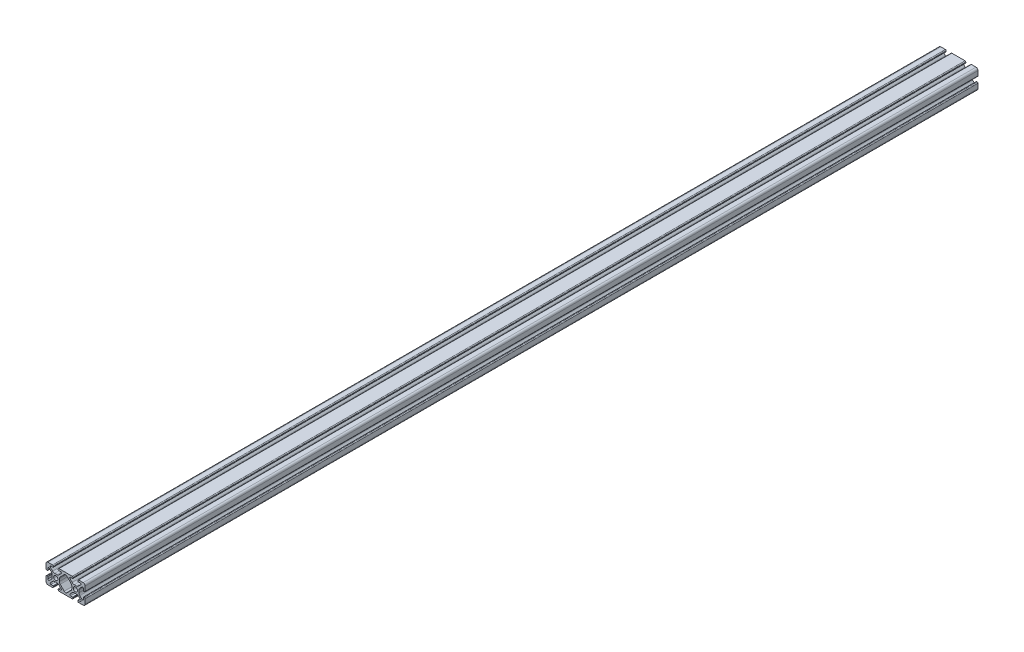
SolidWorks part; units mm, degrees
ref_plane "Plan de face" through (0, 0, 0) normal (0, 0, 1) x (1, 0, 0)
ref_plane "Plan de dessus" through (0, 0, 0) normal (0, 1, 0) x (1, 0, 0)
ref_plane "Plan de droite" through (0, 0, 0) normal (1, 0, 0) x (0, 0, -1)
ref_plane "Plan1" through (0, 0, 0) normal (0, 0, -1) x (-1, 0, 0)
sketch "Esquisse1" plane through (0, 0, 0) normal (0, 0, -1) x (-1, 0, 0)
  line L0 (-40, 6.7) -> (-40, 2)
  line L1 (-38, 0) -> (-33.3, 0)
  line L2 (-32.5, 0.8) -> (-32.5, 1.5)
  line L3 (-32.8, 1.8) -> (-34.9184, 1.8)
  line L4 (-35.5064, 3.2196) -> (-33.2547, 5.4713)
  line L5 (-31.1334, 6.35) -> (-28.8666, 6.35)
  line L6 (-26.7453, 5.4713) -> (-24.4936, 3.2196)
  line L7 (-25.0816, 1.8) -> (-27.2, 1.8)
  line L8 (-27.5, 1.5) -> (-27.5, 0.8)
  line L9 (-26.7, 0) -> (-13.3, 0)
  line L10 (-12.5, 0.8) -> (-12.5, 1.5)
  line L11 (-12.8, 1.8) -> (-14.9184, 1.8)
  line L12 (-15.5064, 3.2196) -> (-13.2547, 5.4713)
  line L13 (-11.1334, 6.35) -> (-8.8666, 6.35)
  line L14 (-6.7453, 5.4713) -> (-4.4936, 3.2196)
  line L15 (-5.0816, 1.8) -> (-7.2, 1.8)
  line L16 (-7.5, 1.5) -> (-7.5, 0.8)
  line L17 (-6.7, 0) -> (-2, 0)
  line L18 (0, 2) -> (0, 6.7)
  line L19 (-0.8, 7.5) -> (-1.5, 7.5)
  line L20 (-1.8, 7.2) -> (-1.8, 5.0816)
  line L21 (-3.2196, 4.4936) -> (-5.4713, 6.7453)
  line L22 (-6.35, 8.8666) -> (-6.35, 11.1334)
  line L23 (-5.4713, 13.2547) -> (-3.2196, 15.5064)
  line L24 (-1.8, 14.9184) -> (-1.8, 12.8)
  line L25 (-1.5, 12.5) -> (-0.8, 12.5)
  line L26 (0, 13.3) -> (0, 18)
  line L27 (-2, 20) -> (-6.7, 20)
  line L28 (-7.5, 19.2) -> (-7.5, 18.5)
  line L29 (-7.2, 18.2) -> (-5.0816, 18.2)
  line L30 (-4.4936, 16.7804) -> (-6.7453, 14.5287)
  line L31 (-8.8666, 13.65) -> (-11.1334, 13.65)
  line L32 (-13.2547, 14.5287) -> (-15.5064, 16.7804)
  line L33 (-14.9184, 18.2) -> (-12.8, 18.2)
  line L34 (-12.5, 18.5) -> (-12.5, 19.2)
  line L35 (-13.3, 20) -> (-26.7, 20)
  line L36 (-27.5, 19.2) -> (-27.5, 18.5)
  line L37 (-27.2, 18.2) -> (-25.0816, 18.2)
  line L38 (-24.4936, 16.7804) -> (-26.7453, 14.5287)
  line L39 (-28.8666, 13.65) -> (-31.1334, 13.65)
  line L40 (-33.2547, 14.5287) -> (-35.5064, 16.7804)
  line L41 (-34.9184, 18.2) -> (-32.8, 18.2)
  line L42 (-32.5, 18.5) -> (-32.5, 19.2)
  line L43 (-33.3, 20) -> (-38, 20)
  line L44 (-40, 18) -> (-40, 13.3)
  line L45 (-39.2, 12.5) -> (-38.5, 12.5)
  line L46 (-38.2, 12.8) -> (-38.2, 14.9184)
  line L47 (-36.7804, 15.5064) -> (-34.5287, 13.2547)
  line L48 (-33.65, 11.1334) -> (-33.65, 8.8666)
  line L49 (-34.5287, 6.7453) -> (-36.7804, 4.4936)
  line L50 (-38.2, 5.0816) -> (-38.2, 7.2)
  line L51 (-38.5, 7.5) -> (-39.2, 7.5)
  line L52 (-18.5858, 17.313) -> (-14.5287, 13.2559)
  line L53 (-13.65, 11.1346) -> (-13.65, 8.8654)
  line L54 (-14.5287, 6.7441) -> (-18.5858, 2.687)
  line L55 (-21.4142, 2.687) -> (-25.4713, 6.7441)
  line L56 (-26.35, 8.8654) -> (-26.35, 11.1346)
  line L57 (-25.4713, 13.2559) -> (-21.4142, 17.313)
  arc A0 (-39.2, 7.5) -> (-40, 6.7) centre (-39.2, 6.7) ccw
  arc A1 (-40, 2) -> (-38, 0) centre (-38, 2) ccw
  arc A2 (-33.3, 0) -> (-32.5, 0.8) centre (-33.3, 0.8) ccw
  arc A3 (-32.5, 1.5) -> (-32.8, 1.8) centre (-32.8, 1.5) ccw
  arc A4 (-34.9184, 1.8) -> (-35.5064, 3.2196) centre (-34.9184, 2.6316) cw
  arc A5 (-33.2547, 5.4713) -> (-31.1334, 6.35) centre (-31.1334, 3.35) cw
  arc A6 (-28.8666, 6.35) -> (-26.7453, 5.4713) centre (-28.8666, 3.35) cw
  arc A7 (-24.4936, 3.2196) -> (-25.0816, 1.8) centre (-25.0816, 2.6316) cw
  arc A8 (-27.2, 1.8) -> (-27.5, 1.5) centre (-27.2, 1.5) ccw
  arc A9 (-27.5, 0.8) -> (-26.7, 0) centre (-26.7, 0.8) ccw
  arc A10 (-13.3, 0) -> (-12.5, 0.8) centre (-13.3, 0.8) ccw
  arc A11 (-12.5, 1.5) -> (-12.8, 1.8) centre (-12.8, 1.5) ccw
  arc A12 (-14.9184, 1.8) -> (-15.5064, 3.2196) centre (-14.9184, 2.6316) cw
  arc A13 (-13.2547, 5.4713) -> (-11.1334, 6.35) centre (-11.1334, 3.35) cw
  arc A14 (-8.8666, 6.35) -> (-6.7453, 5.4713) centre (-8.8666, 3.35) cw
  arc A15 (-4.4936, 3.2196) -> (-5.0816, 1.8) centre (-5.0816, 2.6316) cw
  arc A16 (-7.2, 1.8) -> (-7.5, 1.5) centre (-7.2, 1.5) ccw
  arc A17 (-7.5, 0.8) -> (-6.7, 0) centre (-6.7, 0.8) ccw
  arc A18 (-2, 0) -> (0, 2) centre (-2, 2) ccw
  arc A19 (0, 6.7) -> (-0.8, 7.5) centre (-0.8, 6.7) ccw
  arc A20 (-1.5, 7.5) -> (-1.8, 7.2) centre (-1.5, 7.2) ccw
  arc A21 (-1.8, 5.0816) -> (-3.2196, 4.4936) centre (-2.6316, 5.0816) cw
  arc A22 (-5.4713, 6.7453) -> (-6.35, 8.8666) centre (-3.35, 8.8666) cw
  arc A23 (-6.35, 11.1334) -> (-5.4713, 13.2547) centre (-3.35, 11.1334) cw
  arc A24 (-3.2196, 15.5064) -> (-1.8, 14.9184) centre (-2.6316, 14.9184) cw
  arc A25 (-1.8, 12.8) -> (-1.5, 12.5) centre (-1.5, 12.8) ccw
  arc A26 (-0.8, 12.5) -> (0, 13.3) centre (-0.8, 13.3) ccw
  arc A27 (0, 18) -> (-2, 20) centre (-2, 18) ccw
  arc A28 (-6.7, 20) -> (-7.5, 19.2) centre (-6.7, 19.2) ccw
  arc A29 (-7.5, 18.5) -> (-7.2, 18.2) centre (-7.2, 18.5) ccw
  arc A30 (-5.0816, 18.2) -> (-4.4936, 16.7804) centre (-5.0816, 17.3684) cw
  arc A31 (-6.7453, 14.5287) -> (-8.8666, 13.65) centre (-8.8666, 16.65) cw
  arc A32 (-11.1334, 13.65) -> (-13.2547, 14.5287) centre (-11.1334, 16.65) cw
  arc A33 (-15.5064, 16.7804) -> (-14.9184, 18.2) centre (-14.9184, 17.3684) cw
  arc A34 (-12.8, 18.2) -> (-12.5, 18.5) centre (-12.8, 18.5) ccw
  arc A35 (-12.5, 19.2) -> (-13.3, 20) centre (-13.3, 19.2) ccw
  arc A36 (-26.7, 20) -> (-27.5, 19.2) centre (-26.7, 19.2) ccw
  arc A37 (-27.5, 18.5) -> (-27.2, 18.2) centre (-27.2, 18.5) ccw
  arc A38 (-25.0816, 18.2) -> (-24.4936, 16.7804) centre (-25.0816, 17.3684) cw
  arc A39 (-26.7453, 14.5287) -> (-28.8666, 13.65) centre (-28.8666, 16.65) cw
  arc A40 (-31.1334, 13.65) -> (-33.2547, 14.5287) centre (-31.1334, 16.65) cw
  arc A41 (-35.5064, 16.7804) -> (-34.9184, 18.2) centre (-34.9184, 17.3684) cw
  arc A42 (-32.8, 18.2) -> (-32.5, 18.5) centre (-32.8, 18.5) ccw
  arc A43 (-32.5, 19.2) -> (-33.3, 20) centre (-33.3, 19.2) ccw
  arc A44 (-38, 20) -> (-40, 18) centre (-38, 18) ccw
  arc A45 (-40, 13.3) -> (-39.2, 12.5) centre (-39.2, 13.3) ccw
  arc A46 (-38.5, 12.5) -> (-38.2, 12.8) centre (-38.5, 12.8) ccw
  arc A47 (-38.2, 14.9184) -> (-36.7804, 15.5064) centre (-37.3684, 14.9184) cw
  arc A48 (-34.5287, 13.2547) -> (-33.65, 11.1334) centre (-36.65, 11.1334) cw
  arc A49 (-33.65, 8.8666) -> (-34.5287, 6.7453) centre (-36.65, 8.8666) cw
  arc A50 (-36.7804, 4.4936) -> (-38.2, 5.0816) centre (-37.3684, 5.0816) cw
  arc A51 (-38.2, 7.2) -> (-38.5, 7.5) centre (-38.5, 7.2) ccw
  circle A52 centre (-10, 10) radius 2.15
  circle A53 centre (-30, 10) radius 2.15
  arc A54 (-21.4142, 17.313) -> (-18.5858, 17.313) centre (-20, 15.8988) cw
  arc A55 (-14.5287, 13.2559) -> (-13.65, 11.1346) centre (-16.65, 11.1346) cw
  arc A56 (-13.65, 8.8654) -> (-14.5287, 6.7441) centre (-16.65, 8.8654) cw
  arc A57 (-18.5858, 2.687) -> (-21.4142, 2.687) centre (-20, 4.1012) cw
  arc A58 (-25.4713, 6.7441) -> (-26.35, 8.8654) centre (-23.35, 8.8654) cw
  arc A59 (-26.35, 11.1346) -> (-25.4713, 13.2559) centre (-23.35, 11.1346) cw
extrude "Boss.-Extru.1" add sketch "Esquisse1" against normal mid plane 912
ref_point "Point1"
ref_point "Point2"
ref_axis "Axis2" through (20, 20, 0) along (0, 1, 0)
